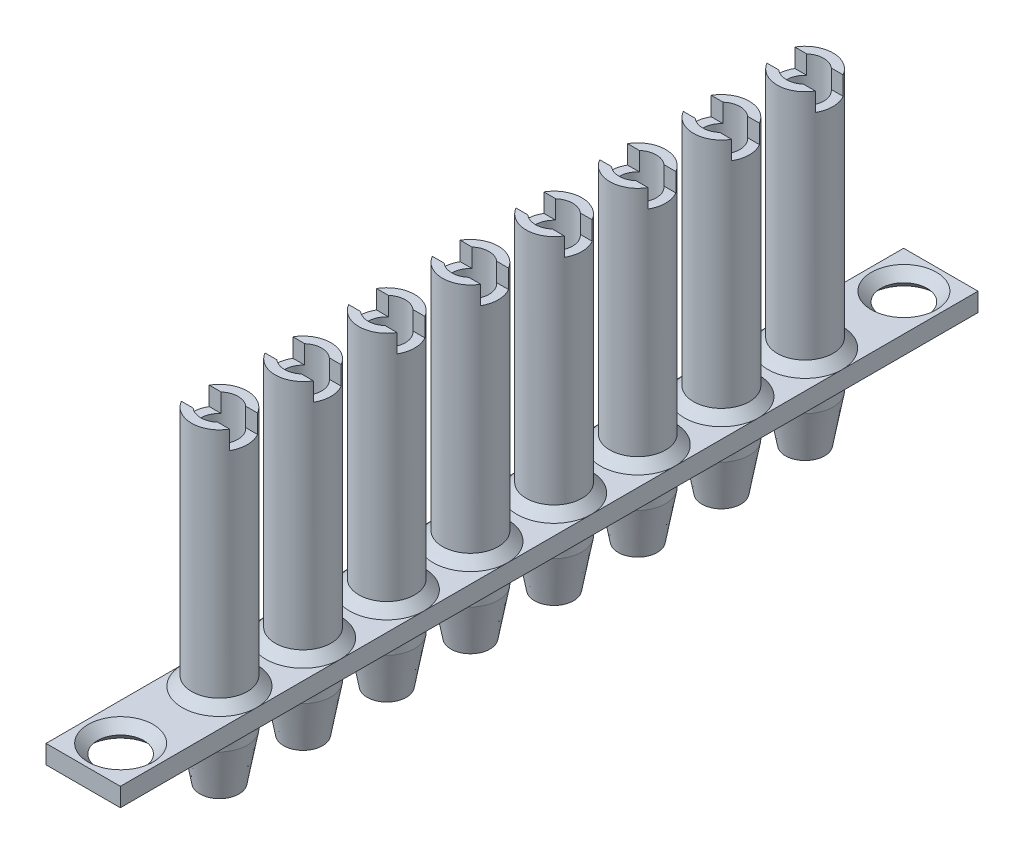
SolidWorks part; units mm, degrees
ref_plane "Front Plane" through (0, 0, 0) normal (0, 0, 1) x (1, 0, 0)
ref_plane "Top Plane" through (0, 0, 0) normal (0, 1, 0) x (1, 0, 0)
ref_plane "Right Plane" through (0, 0, 0) normal (1, 0, 0) x (0, 0, -1)
sketch "Sketch1" plane through (0, 0, 0) normal (0, 0, 1) x (1, 0, 0)
  line L0 (0, 0) -> (0, 30) construction
  line L1 (0, 30) -> (3, 30)
  line L5 (3, 30) -> (3, 0)
  line L6 (3, 0) -> (2.1, -5)
  line L7 (2.1, -5) -> (0, -5)
  line L8 (0, 0) -> (0, -5) construction
  line L9 (3, 0) -> (0, 0) construction
  line L10 (0, 30) -> (0, -5)
  dimension "D1" = 3
  dimension "D2" = 2.1
  dimension "D3" = 30
  dimension "D4" = 5
revolve "Revolve1" add sketch "Sketch1" angle 360 about L10
ref_plane "Plane2" through (0, 0, 0) normal (1, 0, 0) x (0, 0, -1)
shell "Shell1" thickness 1 removed face at (-2.1, -5, 0) removed face at (-3, 30, 0)
pattern_linear "LPattern1" count 8 spacing 9 along (0, 0, 1) of bodies 102
ref_plane "Plane1" through (0, 3, 0) normal (0, -1, 0) x (-1, 0, 0)
sketch "Sketch3" plane through (0, 3, 0) normal (0, -1, 0) x (-1, 0, 0)
  line L0 (0, -3.0549) -> (0, -60) construction
  line L1 (0, -77.6575) -> (0, 14.6025) construction
  line L2 (-4, 14.6025) -> (4, 14.6025)
  line L3 (-4, 14.6025) -> (-4, -77.6575)
  line L4 (-4, -77.6575) -> (4, -77.6575)
  line L5 (4, 14.6025) -> (4, -77.6575)
  line L6 (-4, 14.6025) -> (4, -77.6575) construction
  line L7 (-4, -77.6575) -> (4, 14.6025) construction
  line L8 (4, -31.5275) -> (-4, -31.5275) construction
  circle A0 centre (0, -63) radius 3 construction
  point P5 (0, -31.5275)
  dimension "D1" = 8
  dimension "D2" = 92.26
  dimension "D3" = 4
  dimension "D4" = 31.5275
extrude "Boss-Extrude1" add sketch "Sketch3" along normal mid plane 2
chamfer "Chamfer1" distance 1 angle 45 16 edges at (0, 2, 15) (0, 2, 6) (0, 2, 24) (0, 2, 42) (0, 2, 60) (0, 2, 51) (0, 4, 51) (0, 4, 60) (0, 4, 33) (0, 4, 24) (0, 4, 15) (0, 4, 6) (0, 4, -3) (0, 2, -3) (0, 4, 42) (0, 2, 33)
sketch "Sketch4" plane through (0, 4, 0) normal (0, 1, 0) x (1, 0, 0)
  line L0 (0, -77.6575) -> (0, 14.6025) construction
  line L1 (4, -77.6575) -> (-4, -77.6575) construction
  line L2 (-4, 14.6025) -> (4, 14.6025) construction
  line L3 (4, -31.5) -> (-4, -31.5) construction
  line L4 (4, -27) -> (4, -36) construction
  line L5 (-4, -36) -> (-4, -27) construction
  circle A0 centre (0, -73.63) radius 2.5
  circle A1 centre (0, 10.63) radius 2.5
  dimension "D1" = 5
  dimension "D2" = 84.26
  dimension "D3" = 42.13
  dimension "D4" = 42.13
extrude "Cut-Extrude1" cut sketch "Sketch4" against normal through all
chamfer "Chamfer2" distance 1 angle 45 4 edges at (0, 4, 76.13) (0, 2, 71.13) (0, 2, -13.13) (0, 4, -8.13)
sketch "Sketch5" plane through (0, 0, 0) normal (1, 0, 0) x (0, 0, -1)
  line L0 (0, 30) -> (0, 5) construction
  line L1 (2, 30) -> (-2, 30) construction
  line L2 (3, 5) -> (-3, 5) construction
  line L4 (1.5, 30) -> (-1.5, 30)
  line L5 (1.5, 30) -> (1.5, 28)
  line L6 (1.5, 28) -> (-1.5, 28)
  line L7 (-1.5, 30) -> (-1.5, 28)
  line L8 (1.5, 30) -> (-1.5, 28) construction
  line L9 (1.5, 28) -> (-1.5, 30) construction
  point P6 (0, 29)
  dimension "D1" = 2
  dimension "D2" = 3
extrude "Cut-Extrude2" cut sketch "Sketch5" against normal through all both and the other way through all
pattern_linear "LPattern2" count 8 spacing 9 along (0, 0, 1) of "Cut-Extrude2"
